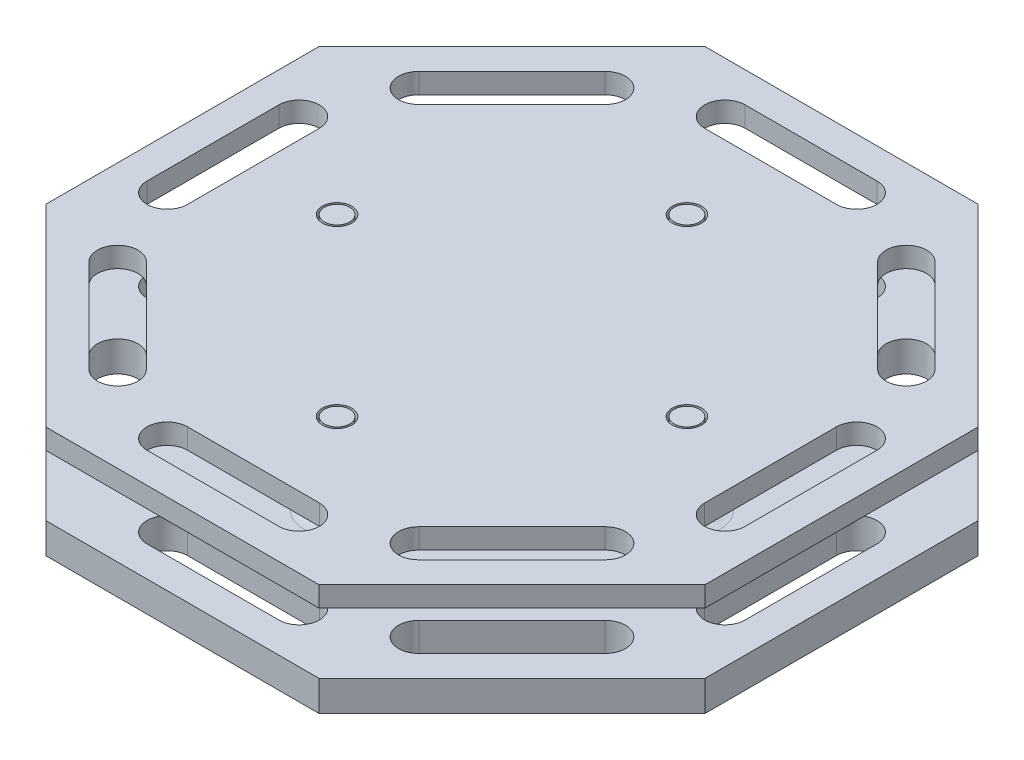
SolidWorks part; units mm, degrees
ref_plane "Front Plane" through (0, 0, 0) normal (0, 0, 1) x (1, 0, 0)
ref_plane "Top Plane" through (0, 0, 0) normal (0, 1, 0) x (1, 0, 0)
ref_plane "Right Plane" through (0, 0, 0) normal (1, 0, 0) x (0, 0, -1)
sketch "Sketch1" plane through (0, 0, 0) normal (0, 1, 0) x (1, 0, 0)
  line L0 (0, 0) -> (-17.78, 5.969) construction
  line L1 (41.275, 17.0967) -> (17.0967, 41.275)
  line L2 (17.0967, 41.275) -> (-17.0967, 41.275)
  line L3 (-17.0967, 41.275) -> (-41.275, 17.0967)
  line L4 (-41.275, 17.0967) -> (-41.275, -17.0967)
  line L5 (-41.275, -17.0967) -> (-17.0967, -41.275)
  line L6 (-17.0967, -41.275) -> (17.0967, -41.275)
  line L7 (17.0967, -41.275) -> (41.275, -17.0967)
  line L8 (41.275, -17.0967) -> (41.275, 17.0967)
  line L9 (0, 0) -> (5.969, 17.78) construction
  line L10 (-8.255, 34.925) -> (8.255, 34.925) construction
  line L11 (-8.255, 37.465) -> (8.255, 37.465)
  line L12 (-8.255, 32.385) -> (8.255, 32.385)
  line L13 (17.0625, 28.7368) -> (28.7368, 17.0625)
  line L14 (20.6546, 32.3289) -> (32.3289, 20.6546)
  line L15 (18.8585, 30.5329) -> (30.5329, 18.8585) construction
  line L16 (32.385, 8.255) -> (32.385, -8.255)
  line L17 (37.465, 8.255) -> (37.465, -8.255)
  line L18 (34.925, 8.255) -> (34.925, -8.255) construction
  line L19 (28.7368, -17.0625) -> (17.0625, -28.7368)
  line L20 (32.3289, -20.6546) -> (20.6546, -32.3289)
  line L21 (30.5329, -18.8585) -> (18.8585, -30.5329) construction
  line L22 (8.255, -32.385) -> (-8.255, -32.385)
  line L23 (8.255, -37.465) -> (-8.255, -37.465)
  line L24 (8.255, -34.925) -> (-8.255, -34.925) construction
  line L25 (-17.0625, -28.7368) -> (-28.7368, -17.0625)
  line L26 (-20.6546, -32.3289) -> (-32.3289, -20.6546)
  line L27 (-18.8585, -30.5329) -> (-30.5329, -18.8585) construction
  line L28 (-32.385, -8.255) -> (-32.385, 8.255)
  line L29 (-37.465, -8.255) -> (-37.465, 8.255)
  line L30 (-34.925, -8.255) -> (-34.925, 8.255) construction
  line L31 (-28.7368, 17.0625) -> (-17.0625, 28.7368)
  line L32 (-32.3289, 20.6546) -> (-20.6546, 32.3289)
  line L33 (-30.5329, 18.8585) -> (-18.8585, 30.5329) construction
  line L34 (0, 0) -> (8.255, 32.385) construction
  circle A0 centre (0, 0) radius 41.275 construction
  circle A1 centre (-17.78, 5.969) radius 1.5
  circle A2 centre (-17.78, -5.969) radius 1.5
  circle A3 centre (5.969, 17.78) radius 1.5
  circle A4 centre (-5.969, 17.78) radius 1.5
  circle A5 centre (17.78, -5.969) radius 1.5
  circle A6 centre (17.78, 5.969) radius 1.5
  circle A7 centre (-5.969, -17.78) radius 1.5
  circle A8 centre (5.969, -17.78) radius 1.5
  arc A9 (-8.255, 37.465) -> (-8.255, 32.385) centre (-8.255, 34.925) ccw
  arc A10 (8.255, 32.385) -> (8.255, 37.465) centre (8.255, 34.925) ccw
  arc A11 (20.6546, 32.3289) -> (17.0625, 28.7368) centre (18.8585, 30.5329) ccw
  arc A12 (28.7368, 17.0625) -> (32.3289, 20.6546) centre (30.5329, 18.8585) ccw
  arc A13 (37.465, 8.255) -> (32.385, 8.255) centre (34.925, 8.255) ccw
  arc A14 (32.385, -8.255) -> (37.465, -8.255) centre (34.925, -8.255) ccw
  arc A15 (32.3289, -20.6546) -> (28.7368, -17.0625) centre (30.5329, -18.8585) ccw
  arc A16 (17.0625, -28.7368) -> (20.6546, -32.3289) centre (18.8585, -30.5329) ccw
  arc A17 (8.255, -37.465) -> (8.255, -32.385) centre (8.255, -34.925) ccw
  arc A18 (-8.255, -32.385) -> (-8.255, -37.465) centre (-8.255, -34.925) ccw
  arc A19 (-20.6546, -32.3289) -> (-17.0625, -28.7368) centre (-18.8585, -30.5329) ccw
  arc A20 (-28.7368, -17.0625) -> (-32.3289, -20.6546) centre (-30.5329, -18.8585) ccw
  arc A21 (-37.465, -8.255) -> (-32.385, -8.255) centre (-34.925, -8.255) ccw
  arc A22 (-32.385, 8.255) -> (-37.465, 8.255) centre (-34.925, 8.255) ccw
  arc A23 (-32.3289, 20.6546) -> (-28.7368, 17.0625) centre (-30.5329, 18.8585) ccw
  arc A24 (-17.0625, 28.7368) -> (-20.6546, 32.3289) centre (-18.8585, 30.5329) ccw
  point P17 (0, 34.925)
  point P41 (24.6957, 24.6957)
  point P48 (34.925, 0)
  point P55 (24.6957, -24.6957)
  point P62 (0, -34.925)
  point P69 (-24.6957, -24.6957)
  point P76 (-34.925, 0)
  point P83 (-24.6957, 24.6957)
  dimension "D2" = 3
  dimension "D9" = 2.54
  dimension "D3" = 17.78
  dimension "D4" = 5.969
  dimension "D5" = 11.938
  dimension "D7" = 90
  dimension "D8" = 82.55
  dimension "D10" = 16.51
  dimension "D12" = 3.81
  dimension "D6" = 4
  dimension "D11" = 8
extrude "Boss-Extrude1" add sketch "Sketch1" along normal blind 3.81
sketch "Sketch2" plane through (0, 3.81, 0) normal (0, 1, 0) x (1, 0, 0)
  line L0 (0, 41.275) -> (0, -41.275) construction
  line L1 (17.0967, 41.275) -> (-17.0967, 41.275) construction
  line L2 (-17.0967, -41.275) -> (17.0967, -41.275) construction
  line L3 (-41.275, 0) -> (41.275, 0) construction
  line L4 (-41.275, 17.0967) -> (-41.275, -17.0967) construction
  line L5 (41.275, -17.0967) -> (41.275, 17.0967) construction
  line L6 (0, -21.9118) -> (21.9118, 0) construction
  line L7 (-21.9118, 0) -> (0, 21.9118) construction
  circle A4 centre (-21.9118, 0) radius 1.5875
  circle A5 centre (21.9118, 0) radius 1.5875
  circle A6 centre (0, 21.9118) radius 1.5875
  circle A7 centre (0, -21.9118) radius 1.5875
  dimension "D5" = 45
  dimension "D10" = 3.175
  dimension "D2" = 30.988
  dimension "D3" = 30.988
  dimension "D4" = 45
extrude "Boss-Extrude2" add sketch "Sketch2" along normal blind 10.16
fillet "Fillet1" radius 2.54 4 edges at (0, 3.81, 23.4993) (21.9118, 3.81, 1.5875) (0, 3.81, -20.3243) (-21.9118, 3.81, 1.5875)
sketch "Sketch3" plane through (0, 13.97, 0) normal (0, 1, 0) x (1, 0, 0)
  line L5 (-37.465, 8.255) -> (-37.465, -8.255) construction
  line L6 (-37.465, 8.255) -> (-37.465, -8.255)
  line L7 (-32.3289, -20.6546) -> (-20.6546, -32.3289) construction
  line L8 (41.275, -17.0967) -> (41.275, 17.0967)
  line L9 (41.275, 17.0967) -> (17.0967, 41.275)
  line L10 (17.0967, 41.275) -> (-17.0967, 41.275)
  line L11 (-17.0967, 41.275) -> (-41.275, 17.0967)
  line L12 (-41.275, 17.0967) -> (-41.275, -17.0967)
  line L13 (-41.275, -17.0967) -> (-17.0967, -41.275)
  line L14 (-17.0967, -41.275) -> (17.0967, -41.275)
  line L15 (17.0967, -41.275) -> (41.275, -17.0967)
  line L16 (41.275, -17.0967) -> (41.275, 17.0967)
  line L17 (41.275, 17.0967) -> (17.0967, 41.275)
  line L18 (17.0967, 41.275) -> (-17.0967, 41.275)
  line L19 (-17.0967, 41.275) -> (-41.275, 17.0967)
  line L20 (-41.275, 17.0967) -> (-41.275, -17.0967)
  line L21 (-41.275, -17.0967) -> (-17.0967, -41.275)
  line L22 (-17.0967, -41.275) -> (17.0967, -41.275)
  line L23 (17.0967, -41.275) -> (41.275, -17.0967)
  line L24 (-17.0625, -28.7368) -> (-28.7368, -17.0625) construction
  line L25 (-8.255, -37.465) -> (8.255, -37.465) construction
  line L26 (8.255, -32.385) -> (-8.255, -32.385) construction
  line L27 (20.6546, -32.3289) -> (32.3289, -20.6546) construction
  line L28 (28.7368, -17.0625) -> (17.0625, -28.7368) construction
  line L29 (37.465, -8.255) -> (37.465, 8.255) construction
  line L30 (32.385, 8.255) -> (32.385, -8.255) construction
  line L31 (17.0625, 28.7368) -> (28.7368, 17.0625) construction
  line L32 (32.3289, 20.6546) -> (20.6546, 32.3289) construction
  line L33 (-8.255, 32.385) -> (8.255, 32.385) construction
  line L34 (8.255, 37.465) -> (-8.255, 37.465) construction
  line L35 (-20.6546, 32.3289) -> (-32.3289, 20.6546) construction
  line L36 (-28.7368, 17.0625) -> (-17.0625, 28.7368) construction
  line L37 (-32.385, -8.255) -> (-32.385, 8.255) construction
  line L38 (-32.3289, -20.6546) -> (-20.6546, -32.3289)
  line L39 (-17.0625, -28.7368) -> (-28.7368, -17.0625)
  line L40 (-8.255, -37.465) -> (8.255, -37.465)
  line L41 (8.255, -32.385) -> (-8.255, -32.385)
  line L42 (20.6546, -32.3289) -> (32.3289, -20.6546)
  line L43 (28.7368, -17.0625) -> (17.0625, -28.7368)
  line L44 (37.465, -8.255) -> (37.465, 8.255)
  line L45 (32.385, 8.255) -> (32.385, -8.255)
  line L46 (17.0625, 28.7368) -> (28.7368, 17.0625)
  line L47 (32.3289, 20.6546) -> (20.6546, 32.3289)
  line L48 (-8.255, 32.385) -> (8.255, 32.385)
  line L49 (8.255, 37.465) -> (-8.255, 37.465)
  line L50 (-20.6546, 32.3289) -> (-32.3289, 20.6546)
  line L51 (-28.7368, 17.0625) -> (-17.0625, 28.7368)
  line L52 (-32.385, -8.255) -> (-32.385, 8.255)
  arc A5 (-37.465, -8.255) -> (-32.385, -8.255) centre (-34.925, -8.255) ccw construction
  arc A6 (-37.465, -8.255) -> (-32.385, -8.255) centre (-34.925, -8.255) ccw
  circle A7 centre (0, -21.9118) radius 1.5875 construction
  circle A8 centre (21.9118, 0) radius 1.5875 construction
  circle A9 centre (0, 21.9118) radius 1.5875 construction
  circle A10 centre (-21.9118, 0) radius 1.5875 construction
  arc A11 (-28.7368, -17.0625) -> (-32.3289, -20.6546) centre (-30.5329, -18.8585) ccw construction
  arc A12 (-20.6546, -32.3289) -> (-17.0625, -28.7368) centre (-18.8585, -30.5329) ccw construction
  arc A13 (-8.255, -32.385) -> (-8.255, -37.465) centre (-8.255, -34.925) ccw construction
  arc A14 (8.255, -37.465) -> (8.255, -32.385) centre (8.255, -34.925) ccw construction
  arc A15 (17.0625, -28.7368) -> (20.6546, -32.3289) centre (18.8585, -30.5329) ccw construction
  arc A16 (32.3289, -20.6546) -> (28.7368, -17.0625) centre (30.5329, -18.8585) ccw construction
  arc A17 (32.385, -8.255) -> (37.465, -8.255) centre (34.925, -8.255) ccw construction
  arc A18 (37.465, 8.255) -> (32.385, 8.255) centre (34.925, 8.255) ccw construction
  arc A19 (28.7368, 17.0625) -> (32.3289, 20.6546) centre (30.5329, 18.8585) ccw construction
  arc A20 (20.6546, 32.3289) -> (17.0625, 28.7368) centre (18.8585, 30.5329) ccw construction
  arc A21 (8.255, 32.385) -> (8.255, 37.465) centre (8.255, 34.925) ccw construction
  arc A22 (-8.255, 37.465) -> (-8.255, 32.385) centre (-8.255, 34.925) ccw construction
  arc A23 (-17.0625, 28.7368) -> (-20.6546, 32.3289) centre (-18.8585, 30.5329) ccw construction
  arc A24 (-32.3289, 20.6546) -> (-28.7368, 17.0625) centre (-30.5329, 18.8585) ccw construction
  arc A25 (-32.385, 8.255) -> (-37.465, 8.255) centre (-34.925, 8.255) ccw construction
  circle A26 centre (0, -21.9118) radius 1.5875
  circle A27 centre (21.9118, 0) radius 1.5875
  circle A28 centre (0, 21.9118) radius 1.5875
  circle A29 centre (-21.9118, 0) radius 1.5875
  arc A30 (-28.7368, -17.0625) -> (-32.3289, -20.6546) centre (-30.5329, -18.8585) ccw
  arc A31 (-20.6546, -32.3289) -> (-17.0625, -28.7368) centre (-18.8585, -30.5329) ccw
  arc A32 (-8.255, -32.385) -> (-8.255, -37.465) centre (-8.255, -34.925) ccw
  arc A33 (8.255, -37.465) -> (8.255, -32.385) centre (8.255, -34.925) ccw
  arc A34 (17.0625, -28.7368) -> (20.6546, -32.3289) centre (18.8585, -30.5329) ccw
  arc A35 (32.3289, -20.6546) -> (28.7368, -17.0625) centre (30.5329, -18.8585) ccw
  arc A36 (32.385, -8.255) -> (37.465, -8.255) centre (34.925, -8.255) ccw
  arc A37 (37.465, 8.255) -> (32.385, 8.255) centre (34.925, 8.255) ccw
  arc A38 (28.7368, 17.0625) -> (32.3289, 20.6546) centre (30.5329, 18.8585) ccw
  arc A39 (20.6546, 32.3289) -> (17.0625, 28.7368) centre (18.8585, 30.5329) ccw
  arc A40 (8.255, 32.385) -> (8.255, 37.465) centre (8.255, 34.925) ccw
  arc A41 (-8.255, 37.465) -> (-8.255, 32.385) centre (-8.255, 34.925) ccw
  arc A42 (-17.0625, 28.7368) -> (-20.6546, 32.3289) centre (-18.8585, 30.5329) ccw
  arc A43 (-32.3289, 20.6546) -> (-28.7368, 17.0625) centre (-30.5329, 18.8585) ccw
  arc A44 (-32.385, 8.255) -> (-37.465, 8.255) centre (-34.925, 8.255) ccw
  circle A45 centre (0, 21.9118) radius 1.8415
  circle A46 centre (-21.9118, 0) radius 1.8415
  circle A47 centre (0, -21.9118) radius 1.8415
  circle A48 centre (21.9118, 0) radius 1.8415
  dimension "D1" = 0
  dimension "D2" = 0.254
extrude "Boss-Extrude3" add sketch "Sketch3" against normal blind 2.54 contours L22 L23 L16 L17 L18 L19 L20 L21 A48 A47 A46 A45 A44 L52 A6 L6 A43 L50 A42 L51 A41 L49 A40 L48 A39 L47 A38 L46 A37 L44 A36 L45 A35 L42 A34 L43 A33 L40 A32 L41 region at (0, 13.97, 0)
